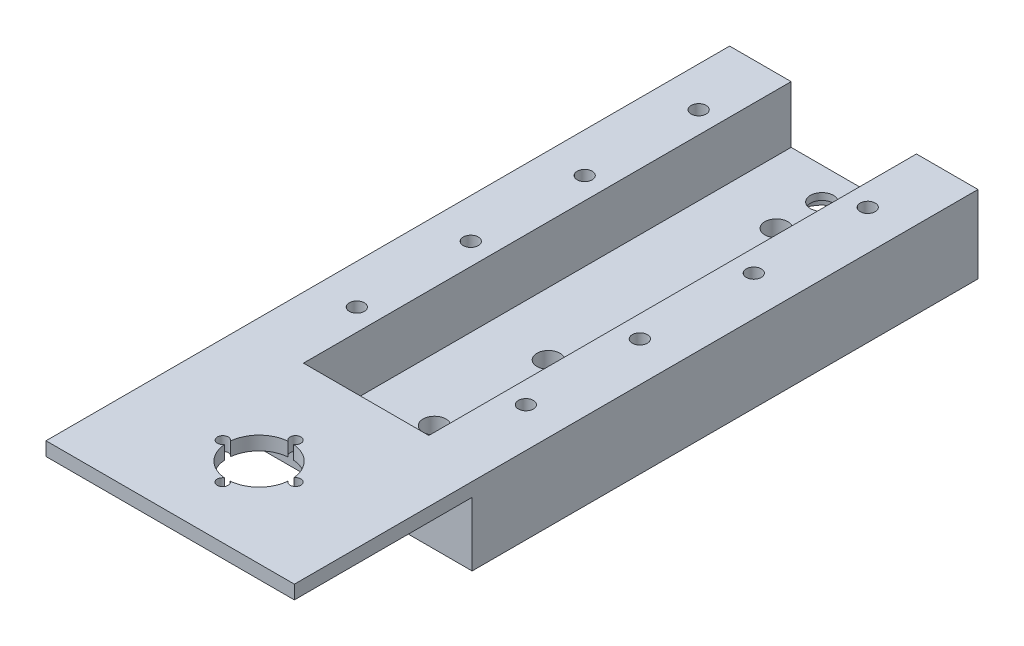
SolidWorks part; units mm, degrees
ref_plane "Front Plane" through (0, 0, 0) normal (0, 0, 1) x (1, 0, 0)
ref_plane "Top Plane" through (0, 0, 0) normal (0, 1, 0) x (1, 0, 0)
ref_plane "Right Plane" through (0, 0, 0) normal (1, 0, 0) x (0, 0, -1)
sketch "Sketch1" plane through (0, 0, 0) normal (0, 1, 0) x (1, 0, 0)
  line L1 (-40.6495, -11.3707) -> (13.8505, -11.3707)
  line L2 (-40.6495, -11.3707) -> (-40.6495, 99.6293)
  line L3 (-40.6495, 99.6293) -> (13.8505, 99.6293)
  line L4 (13.8505, -11.3707) -> (13.8505, 99.6293)
  dimension "D1" = 54.5
  dimension "D2" = 111
extrude "Boss-Extrude1" add sketch "Sketch1" along normal blind 4.5
sketch "Sketch2" plane through (0, 4.5, 0) normal (0, 1, 0) x (1, 0, 0)
  line L0 (13.8505, 99.6293) -> (-40.6495, 99.6293) construction
  line L1 (0.3505, 99.6293) -> (13.8505, 99.6293)
  line L2 (0.3505, 99.6293) -> (0.3505, -11.3707)
  line L3 (0.3505, -11.3707) -> (13.8505, -11.3707)
  line L4 (13.8505, 99.6293) -> (13.8505, -11.3707)
  line L5 (-40.6495, -11.3707) -> (13.8505, -11.3707) construction
  line L6 (-40.6495, 99.6293) -> (-27.1495, 99.6293)
  line L7 (-40.6495, 99.6293) -> (-40.6495, -11.3707)
  line L8 (-40.6495, -11.3707) -> (-27.1495, -11.3707)
  line L9 (-27.1495, 99.6293) -> (-27.1495, -11.3707)
  dimension "D1" = 13.5
  dimension "D2" = 13.5
extrude "Boss-Extrude2" add sketch "Sketch2" along normal blind 12.5 contours L7 L6 L9 L8 | L2 L1 L4 L3
hole_wizard "M4x0.7 Tapped Hole1" positions "3DSketch1" profile "Sketch3" tap size "M4x0.7" standard "ANSI Metric" end condition through all
sketch3d "3DSketch1"
  line L0 (-40.6495, 17, -99.6293) -> (-27.1495, 17, -99.6293) construction
  line L1 (-40.6495, 17, -99.6293) -> (-40.6495, 17, 11.3707) construction
  line L2 (-40.6495, 17, 11.3707) -> (-27.1495, 17, 11.3707) construction
  line L3 (0.3505, 17, -99.6293) -> (13.8505, 17, -99.6293) construction
  line L4 (13.8505, 17, -99.6293) -> (13.8505, 17, 11.3707) construction
  point P0 (-31.9495, 17, -9.1293)
  point P2 (-31.9495, 17, -34.1293)
  point P4 (-31.9495, 17, -59.1293)
  point P6 (-31.9495, 17, -84.1293)
  point P8 (5.1505, 17, -9.1293)
  point P10 (5.1505, 17, -34.1293)
  point P12 (5.1505, 17, -59.1293)
  point P14 (5.1505, 17, -84.1293)
  dimension "D1" = 15.5
  dimension "D2" = 8.7
  dimension "D3" = 25
  dimension "D4" = 8.7
  dimension "D5" = 25
  dimension "D6" = 8.7
  dimension "D7" = 25
  dimension "D8" = 8.7
  dimension "D9" = 20.5
  dimension "D10" = 15.5
  dimension "D11" = 8.7
  dimension "D12" = 25
  dimension "D13" = 8.7
  dimension "D14" = 25
  dimension "D15" = 8.7
  dimension "D16" = 8.7
  dimension "D17" = 25
sketch "Sketch3" plane through (-31.9495, 17, -9.1293) normal (1, 0, 0) x (0, 0, 1)
  line L0 (0, 0) -> (0, 17)
  line L1 (0, 17) -> (1.65, 17)
  line L2 (1.65, 17) -> (1.65, 0)
  line L5 (1.65, 0) -> (0, 0)
  line L11 (0, -6.35) -> (0, 107.95) construction
  dimension "Thru Tap Drill Dia." = 3.3
  dimension "Thru Tap Drill Depth" = 17
cosmetic thread "Hole Thread1" parameters "D2"=4
cosmetic thread "Hole Thread2" parameters "D2"=4
cosmetic thread "Hole Thread3" parameters "D2"=4
cosmetic thread "Hole Thread4" parameters "D2"=4
cosmetic thread "Hole Thread5" parameters "D2"=4
cosmetic thread "Hole Thread6" parameters "D2"=4
cosmetic thread "Hole Thread7" parameters "D2"=4
cosmetic thread "Hole Thread8" parameters "D2"=4
sketch "Sketch6" plane through (-27.1495, 0, 0) normal (1, 0, 0) x (0, 0, -1)
  line L0 (99.6293, 4.5) -> (-11.3707, 4.5) construction
  line L1 (-11.3707, 17) -> (-7.3707, 17)
  line L2 (-11.3707, 17) -> (-11.3707, 4.5)
  line L3 (-11.3707, 4.5) -> (-7.3707, 4.5)
  line L4 (-7.3707, 17) -> (-7.3707, 4.5)
  dimension "D1" = 4
extrude "Boss-Extrude3" add sketch "Sketch6" along normal blind 37
sketch "Sketch7" plane through (0, 0, 11.3707) normal (0, 0, 1) x (1, 0, 0)
  line L0 (13.8505, 17) -> (13.8505, 0) construction
  line L1 (-40.6495, 17) -> (13.8505, 17)
  line L2 (-40.6495, 17) -> (-40.6495, 14)
  line L3 (-40.6495, 14) -> (13.8505, 14)
  line L4 (13.8505, 17) -> (13.8505, 14)
  dimension "D1" = 3
extrude "Boss-Extrude5" add sketch "Sketch7" along normal blind 39
sketch "Sketch8" plane through (0, 17, 0) normal (0, 1, 0) x (1, 0, 0)
  line L1 (-40.6495, 99.6293) -> (-40.6495, -50.3707) construction
  circle A0 centre (-13.3995, -30.8707) radius 7
  dimension "D1" = 19.5
  dimension "D2" = 27.25
extrude "Cut-Extrude1" cut sketch "Sketch8" against normal blind 3 contours A0
hole_wizard "M2 Clearance Hole1" positions "3DSketch2" profile "Sketch9" hole size "M2" standard "ANSI Metric" end condition through all
sketch3d "3DSketch2"
  line L0 (13.8505, 17, 50.3707) -> (-40.6495, 17, 50.3707) construction
  line L1 (13.8505, 17, -99.6293) -> (13.8505, 17, 50.3707) construction
  point P0 (-21.3714, 17, 30.8479)
  point P2 (-13.3995, 17, 22.8707)
  point P4 (-13.3995, 17, 38.8707)
  point P12 (-5.4305, 17, 30.8451)
  dimension "D1" = 11.5
  dimension "D2" = 16
  dimension "D3" = 27.25
  dimension "D4" = 27.25
  dimension "D5" = 11.31
  dimension "D6" = 11.31
sketch "Sketch9" plane through (-21.3714, 17, 30.8479) normal (1, 0, 0) x (0, 0, 1)
  line L0 (0, 0) -> (0, 17)
  line L1 (0, 17) -> (1.2, 17)
  line L2 (1.2, 17) -> (1.2, 0)
  line L5 (1.2, 0) -> (0, 0)
  line L11 (0, -6.35) -> (0, 107.95) construction
  dimension "Thru Hole Dia." = 2.4
  dimension "Thru Hole Depth" = 17
hole_wizard "#8 (0.199) Diameter Hole1" positions "3DSketch4" profile "Sketch10" hole size "#8" standard "Progressive" end condition through all
sketch3d "3DSketch4"
  line L4 (0.3505, 4.5, -99.6293) -> (0.3505, 4.5, 7.3707) construction
  line L6 (0.3505, 4.5, 7.3707) -> (-27.1495, 4.5, 7.3707) construction
  line L7 (0.3505, 4.5, -99.6293) -> (-27.1495, 4.5, -99.6293) construction
  point P0 (-13.3995, 4.5, 2.3707)
  point P2 (-13.3995, 4.5, -7.6293)
  point P4 (-13.3995, 4.5, -32.6293)
  point P6 (-13.3995, 4.5, -82.6293)
  point P8 (-13.3995, 4.5, -92.6293)
  dimension "D1" = 13.75
  dimension "D2" = 13.75
  dimension "D4" = 13.75
  dimension "D3" = 13.75
  dimension "D5" = 13.75
  dimension "D6" = 5
  dimension "10" = 10
  dimension "D7" = 7
  dimension "D8" = 10
  dimension "D9" = 25
sketch "Sketch10" plane through (-13.3995, 4.5, 2.3707) normal (1, 0, 0) x (0, 0, 1)
  line L0 (0, 0) -> (0, 4.5)
  line L1 (0, 4.5) -> (2.5273, 4.5)
  line L2 (2.5273, 4.5) -> (2.5273, 0)
  line L5 (2.5273, 0) -> (0, 0)
  line L11 (0, -6.35) -> (0, 107.95) construction
  dimension "Thru Hole Dia." = 5.0546
  dimension "Thru Hole Depth" = 4.5
sketch "Sketch12" plane through (0, 0, 0) normal (0, -1, 0) x (-1, 0, 0)
  circle A2 centre (13.3995, 92.6293) radius 5.5
extrude "Cut-Extrude3" cut sketch "Sketch12" against normal blind 3
